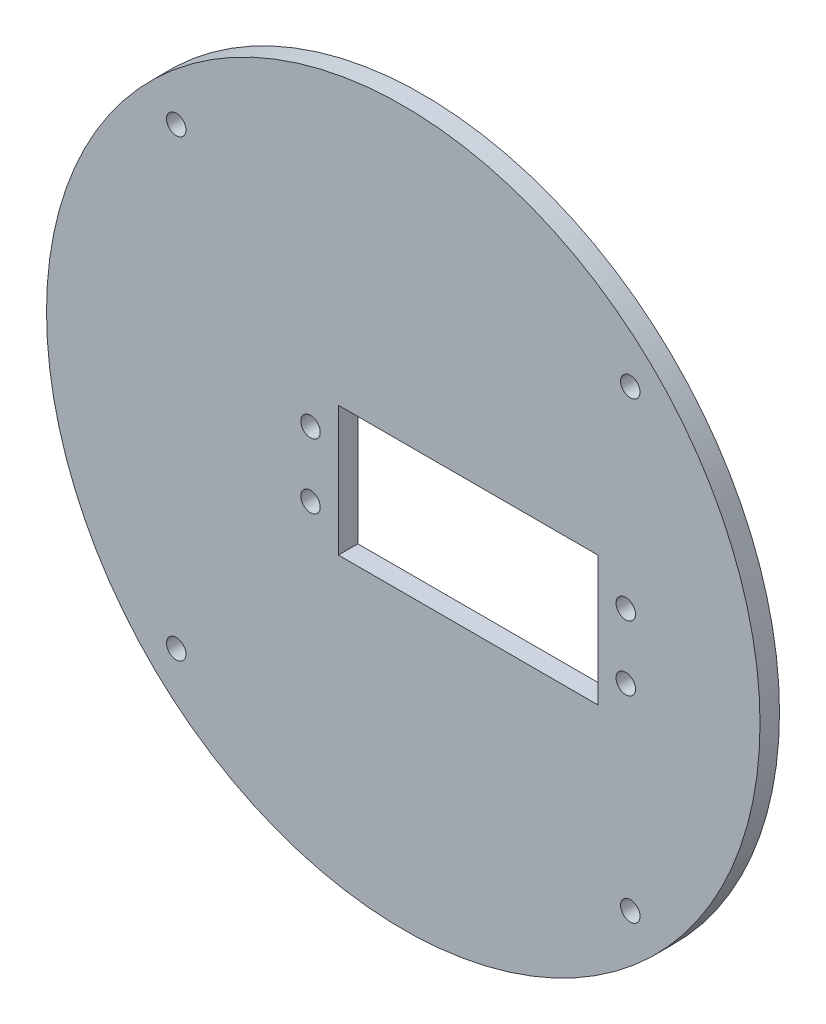
SolidWorks part; units mm, degrees
ref_plane "前视基准面" through (0, 0, 0) normal (0, 0, 1) x (1, 0, 0)
ref_plane "上视基准面" through (0, 0, 0) normal (0, 1, 0) x (1, 0, 0)
ref_plane "右视基准面" through (0, 0, 0) normal (1, 0, 0) x (0, 0, -1)
sketch "草图1" plane through (0, 0, 0) normal (0, 0, 1) x (1, 0, 0)
  line L0 (-35, -35) -> (35, -35)
  line L1 (-35, -35) -> (-35, 35)
  line L2 (-35, 35) -> (35, 35)
  line L3 (35, -35) -> (35, 35)
  line L4 (-35, -35) -> (35, 35) construction
  line L5 (-35, 35) -> (35, -35) construction
  line L7 (-10, 10) -> (30, 10)
  line L8 (-10, 10) -> (-10, -10)
  line L9 (-10, -10) -> (30, -10)
  line L10 (30, 10) -> (30, -10)
  line L11 (-14.3, 5) -> (34.3, 5)
  line L12 (-14.3, 5) -> (-14.3, -5)
  line L13 (-14.3, -5) -> (34.3, -5)
  line L14 (34.3, 5) -> (34.3, -5)
  circle A0 centre (0, 0) radius 55
  circle A1 centre (0, 0) radius 45
  circle A2 centre (-35, 35) radius 1.5
  circle A3 centre (35, 35) radius 1.5
  circle A4 centre (35, -35) radius 1.5
  circle A5 centre (-35, -35) radius 1.5
  circle A6 centre (-14.3, 5) radius 1.5
  circle A7 centre (-14.3, -5) radius 1.5
  circle A8 centre (34.3, 5) radius 1.5
  circle A9 centre (34.3, -5) radius 1.5
  point P16 (-10, 0)
  point P21 (-14.3, 0)
  point P22 (10, 5)
  point P23 (10, 10)
  dimension "D1" = 90
  dimension "D3" = 3
  dimension "D4" = 3
  dimension "D5" = 3
  dimension "D6" = 3
  dimension "D7" = 110
  dimension "D14" = 3
  dimension "D15" = 3
  dimension "D16" = 3
  dimension "D17" = 3
  dimension "D2" = 70
  dimension "D8" = 70
  dimension "D9" = 40
  dimension "D10" = 20
  dimension "D11" = 10
  dimension "D12" = 4.3
  dimension "D13" = 10
extrude "凸台-拉伸2" add sketch "草图1" along normal blind 3 contours A0 A5 L1 A1 A2 L2 A3 L3 A4 L0 | L1 A1 | A9 L13 L10 L9 L8 A7 L12 A6 L11 L7 A8 L3 A1 L2 L1 L0 | L2 A1 | A3 L2 A1 L3 | A9 L3 A1 A8 | L0 A1 | A5 L0 A1 L1 | A7 L13 L8 L11 A6 L12 | A2 L1 A1 L2 | A4 L3 A1 L0 | A9 L14 A8 L11 L10 L13 | A9 L3 A8 L14 region at (-32.7009, -32.7009, 0) region at (-31.1198, -31.1198, 0) region at (0, -39.0407, 0) region at (-39.0407, 0, 0) region at (32.7009, -32.7009, 0) region at (-32.7009, 32.7009, 0) region at (39.07, 0, 0) region at (0, 39.0407, 0) region at (32.7009, 32.7009, 0) region at (34.6528, 0, 0) region at (32.0145, 0, 0) region at (-12.0145, 0, 0) region at (-53.4444, 0, 0)
